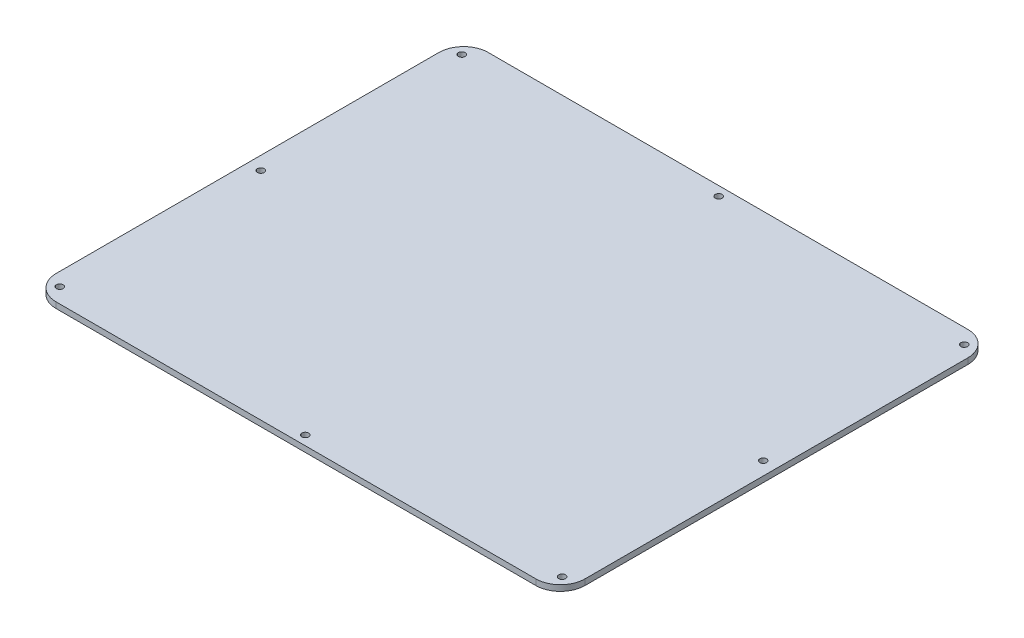
SolidWorks part; units mm, degrees
ref_plane "Front Plane" through (0, 0, 0) normal (0, 0, 1) x (1, 0, 0)
ref_plane "Top Plane" through (0, 0, 0) normal (0, 1, 0) x (1, 0, 0)
ref_plane "Right Plane" through (0, 0, 0) normal (1, 0, 0) x (0, 0, -1)
sketch "Sketch1" plane through (0, 0, 0) normal (0, 1, 0) x (1, 0, 0)
  line L1 (-136.5, -111.5) -> (136.5, -111.5)
  line L2 (-136.5, -111.5) -> (-136.5, 111.5)
  line L3 (-136.5, 111.5) -> (136.5, 111.5)
  line L4 (136.5, -111.5) -> (136.5, 111.5)
  line L5 (-136.5, -111.5) -> (136.5, 111.5) construction
  line L6 (-136.5, 111.5) -> (136.5, -111.5) construction
  point P0 (0, 0)
  dimension "D1" = 273
  dimension "D2" = 223
extrude "Boss-Extrude1" add sketch "Sketch1" along normal blind 3 contours L4 L3 L2 L1
fillet "Fillet1" radius 12.7 4 edges at (136.5, 1.5, 111.5) (-136.5, 1.5, 111.5) (-136.5, 1.5, -111.5) (136.5, 1.5, -111.5)
hole_wizard "Ø3.5 (3.5) Diameter Hole1" positions "Sketch4" profile "Sketch5" hole size "Ø3.5" standard "ANSI Metric" end condition through all
sketch "Sketch4" plane through (0, 0, 0) normal (0, -1, 0) x (-1, 0, 0)
  line L0 (-129.667, -103.759) -> (129.667, 103.759) construction
  line L1 (0, 106.68) -> (0, -106.68) construction
  point P0 (-129.667, 103.759)
  point P2 (0, 106.68)
  point P4 (129.667, 103.759)
  point P6 (129.667, 0)
  point P8 (129.667, -103.759)
  point P10 (0, -106.68)
  point P12 (-129.667, -103.759)
  point P14 (-129.667, 0)
  point P28 (0, 0)
  point P37 (0, 0)
  dimension "D1" = 259.334
  dimension "D2" = 207.518
  dimension "D3" = 213.36
sketch "Sketch5" plane through (129.667, 0, -103.759) normal (1, 0, 0) x (0, 0, -1)
  line L0 (0, 0) -> (0, 3)
  line L1 (0, 3) -> (1.75, 3)
  line L2 (1.75, 3) -> (1.75, 0.025)
  line L3 (1.75, 0.025) -> (1.775, 0)
  line L5 (1.775, 0) -> (0, 0)
  line L6 (-1.75, 0.025) -> (-1.775, 0) construction
  line L11 (0, -6.35) -> (0, 107.95) construction
  dimension "Thru Hole Dia." = 3.5
  dimension "Thru Hole Depth" = 3
  dimension "Near C'Sink Dia." = 3.55
  dimension "Near C'Sink Angle" = 90
sketch "Sketch6" plane through (0, 0, 0) normal (0, -1, 0) x (1, 0, 0)
  line L0 (-136.5, 98.8) -> (-136.5, -98.8) construction
  line L1 (-42.774, 15.113) -> (-73, 15.113)
  line L2 (-42.774, 15.113) -> (-42.774, -15.113)
  line L3 (-42.774, -15.113) -> (-73, -15.113)
  line L4 (-73, 15.113) -> (-73, -15.113)
  line L5 (-42.774, 15.113) -> (-73, -15.113) construction
  line L6 (-42.774, -15.113) -> (-73, 15.113) construction
  point P0 (-57.887, 0)
  dimension "D1" = 30.226
  dimension "D2" = 63.5
extrude "Boss-Extrude2" add sketch "Sketch6" along normal blind 5.08 draft 55
sketch "Sketch8" plane through (0, 0, 0) normal (0, 0, 1) x (1, 0, 0)
  line L1 (-73, -2.0395) -> (-58.0335, -2.0395)
  line L2 (-73, -2.0395) -> (-73, -4.2868)
  line L3 (-73, -4.2868) -> (-58.0335, -4.2868)
  line L4 (-58.0335, -2.0395) -> (-58.0335, -4.2868)
  line L5 (-73, -2.0395) -> (-58.0335, -4.2868) construction
  line L6 (-73, -4.2868) -> (-58.0335, -2.0395) construction
  point P0 (-65.5168, -3.1632)
revolve "Revolve2" add sketch "Sketch8" angle 360 about L1
fillet "Fillet3" radius 1.524 1 edges at (-66.8778, -4.2868, 0)
fillet "Fillet4" radius 1.524 8 edges at (-57.887, -5.08, 7.858) (-50.029, -5.08, 0) (-57.887, -5.08, -7.858) (-65.745, -5.08, 0) (-46.4015, -2.54, 11.4855) (-69.3725, -2.54, 11.4855) (-46.4015, -2.54, -11.4855) (-69.3725, -2.54, -11.4855)
